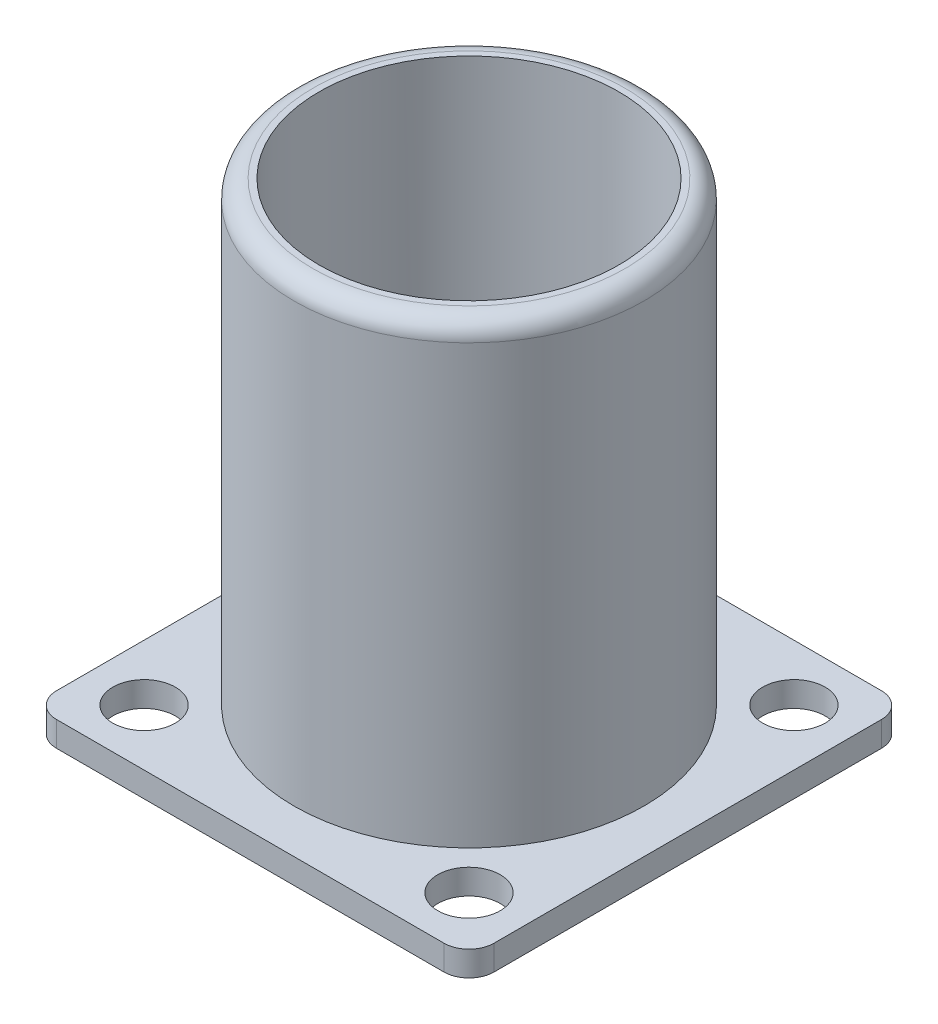
SolidWorks part; units mm, degrees
ref_plane "Plano frontal" through (0, 0, 0) normal (0, 0, 1) x (1, 0, 0)
ref_plane "Plano superior" through (0, 0, 0) normal (0, 1, 0) x (1, 0, 0)
ref_plane "Plano direito" through (0, 0, 0) normal (1, 0, 0) x (0, 0, -1)
sketch "Esboço1" plane through (0, 0, 0) normal (0, 1, 0) x (1, 0, 0)
  line L0 (0, 0) -> (17.5, 0) construction
  line L1 (-17.5, -17.5) -> (17.5, -17.5)
  line L2 (-17.5, -17.5) -> (-17.5, 17.5)
  line L3 (-17.5, 17.5) -> (17.5, 17.5)
  line L4 (17.5, -17.5) -> (17.5, 17.5)
  line L5 (-17.5, -17.5) -> (17.5, 17.5) construction
  line L6 (-17.5, 17.5) -> (17.5, -17.5) construction
  line L7 (-17.5, -13) -> (-13, -13) construction
  line L8 (-17.5, -13) -> (-17.5, -17.5) construction
  line L9 (-17.5, -17.5) -> (-13, -17.5) construction
  line L10 (-13, -13) -> (-13, -17.5) construction
  line L11 (-17.5, -13) -> (-13, -17.5) construction
  line L12 (-17.5, -17.5) -> (-13, -13) construction
  line L13 (0, 0) -> (0, -17.5) construction
  line L14 (0, 0) -> (0, 17.5) construction
  line L15 (-0.75, -11.9765) -> (-0.75, 12)
  line L16 (-12, -12) -> (-10.7087, -12) construction
  line L17 (-12, -12) -> (-12, 12) construction
  line L18 (-12, 12) -> (-0.75, 12) construction
  line L19 (12, -12) -> (12, 12) construction
  line L20 (-12, -12) -> (12, 12) construction
  line L21 (-12, 12) -> (12, -12) construction
  line L22 (0.75, -11.9765) -> (0.75, 12)
  line L23 (0.75, 0) -> (0.75, 17.5) construction
  line L24 (-0.75, 0) -> (-0.75, 17.5) construction
  line L25 (0.75, 12) -> (0.75, 17.5) construction
  line L26 (-0.75, 12) -> (-0.75, 17.5) construction
  line L27 (0.75, -11.9765) -> (0.75, 12)
  line L28 (2.25, -11.9765) -> (2.25, 12)
  line L29 (2.25, -11.9765) -> (2.25, 12)
  line L30 (3.75, -11.9765) -> (3.75, 12)
  line L31 (3.75, -11.9765) -> (3.75, 12)
  line L32 (5.25, -11.9765) -> (5.25, 12)
  line L33 (5.25, -11.9765) -> (5.25, 12)
  line L34 (6.75, -11.9765) -> (6.75, 12)
  line L35 (6.75, -11.9765) -> (6.75, 12)
  line L36 (8.25, -11.9765) -> (8.25, 12)
  line L37 (8.25, -11.9765) -> (8.25, 12)
  line L38 (9.75, -11.9765) -> (9.75, 12)
  line L39 (9.75, -11.9765) -> (9.75, 12)
  line L40 (11.25, -11.9765) -> (11.25, 12)
  line L41 (0, -11.9765) -> (0.75, -11.9765) construction
  line L42 (0, 12) -> (0.75, 12) construction
  line L43 (0.75, 12) -> (12, 12) construction
  line L44 (-0.75, 12) -> (0, 12) construction
  line L45 (-10.7087, -12) -> (0, -12) construction
  line L46 (0, -12) -> (12, -12) construction
  line L47 (-0.75, -11.9765) -> (0, -11.9765) construction
  line L48 (-11.25, -11.9765) -> (-11.25, 12)
  line L49 (-9.75, -11.9765) -> (-9.75, 12)
  line L50 (-8.25, -11.9765) -> (-8.25, 12)
  line L51 (-6.75, -11.9765) -> (-6.75, 12)
  line L52 (-5.25, -11.9765) -> (-5.25, 12)
  line L53 (-3.75, -11.9765) -> (-3.75, 12)
  line L54 (-2.25, -11.9765) -> (-2.25, 12)
  circle A0 centre (-13, -13) radius 2.5
  circle A1 centre (13, -13) radius 2.5
  circle A2 centre (13, 13) radius 2.5
  circle A3 centre (-13, 13) radius 2.5
  arc A4 (-0.75, 11.9765) -> (-2.25, 11.7872) centre (0, 0) ccw
  arc A5 (0.75, 11.9765) -> (0, 12) centre (0, 0) ccw construction
  arc A6 (0, 12) -> (-0.75, 11.9765) centre (0, 0) ccw construction
  arc A7 (-0.75, -11.9765) -> (0, -12) centre (0, 0) ccw construction
  arc A8 (0, -12) -> (2.25, -11.7872) centre (0, 0) ccw
  arc A9 (2.25, -11.7872) -> (3.75, -11.399) centre (0, 0) ccw construction
  arc A10 (3.75, -11.399) -> (5.25, -10.7906) centre (0, 0) ccw
  arc A11 (3.75, 11.399) -> (2.25, 11.7872) centre (0, 0) ccw construction
  arc A12 (2.25, 11.7872) -> (0.75, 11.9765) centre (0, 0) ccw
  arc A13 (6.75, 9.9216) -> (5.25, 10.7906) centre (0, 0) ccw construction
  arc A14 (5.25, 10.7906) -> (3.75, 11.399) centre (0, 0) ccw
  arc A15 (5.25, -10.7906) -> (6.75, -9.9216) centre (0, 0) ccw construction
  arc A16 (6.75, -9.9216) -> (8.4853, -8.4853) centre (0, 0) ccw
  arc A17 (9.75, 6.9955) -> (8.4853, 8.4853) centre (0, 0) ccw construction
  arc A18 (8.4853, 8.4853) -> (6.75, 9.9216) centre (0, 0) ccw
  arc A19 (8.4853, -8.4853) -> (9.75, -6.9955) centre (0, 0) ccw construction
  arc A20 (9.75, -6.9955) -> (11.25, -4.1758) centre (0, 0) ccw
  arc A21 (12, 0) -> (11.25, 4.1758) centre (0, 0) ccw construction
  arc A22 (11.25, 4.1758) -> (9.75, 6.9955) centre (0, 0) ccw
  arc A23 (11.25, -4.1758) -> (12, 0) centre (0, 0) ccw construction
  arc A24 (-2.25, 11.7872) -> (-3.75, 11.399) centre (0, 0) ccw construction
  arc A25 (-3.75, 11.399) -> (-5.25, 10.7906) centre (0, 0) ccw
  arc A26 (-3.75, -11.399) -> (-2.25, -11.7872) centre (0, 0) ccw construction
  arc A27 (-2.25, -11.7872) -> (-0.75, -11.9765) centre (0, 0) ccw
  arc A28 (-6.75, -9.9216) -> (-5.25, -10.7906) centre (0, 0) ccw construction
  arc A29 (-5.25, -10.7906) -> (-3.75, -11.399) centre (0, 0) ccw
  arc A30 (-5.25, 10.7906) -> (-6.75, 9.9216) centre (0, 0) ccw construction
  arc A31 (-6.75, 9.9216) -> (-8.4853, 8.4853) centre (0, 0) ccw
  arc A32 (-8.4853, 8.4853) -> (-9.75, 6.9955) centre (0, 0) ccw construction
  arc A33 (-9.75, 6.9955) -> (-11.25, 4.1758) centre (0, 0) ccw
  arc A34 (-9.75, -6.9955) -> (-8.4853, -8.4853) centre (0, 0) ccw construction
  arc A35 (-8.4853, -8.4853) -> (-6.75, -9.9216) centre (0, 0) ccw
  arc A36 (-12, 0) -> (-11.25, -4.1758) centre (0, 0) ccw construction
  arc A37 (-11.25, -4.1758) -> (-9.75, -6.9955) centre (0, 0) ccw
  arc A38 (-11.25, 4.1758) -> (-12, 0) centre (0, 0) ccw construction
  point P0 (0, 0)
  point P6 (-15.25, -15.25)
  dimension "D3" = 5
  dimension "D4" = 24
  dimension "D1" = 35
  dimension "D2" = 4.5
  dimension "D8" = 1.5
  dimension "D5" = 0.75
  dimension "D6" = 0.75
  dimension "D7" = 8
extrude "Ressalto-extrusão1" add sketch "Esboço1" along normal blind 2 contours L1 L4 L3 L2 A22 A2 L40 A1 A20 L39 A18 L37 A16 L35 A14 L33 A10 L31 A12 region at (0, 0, 0)
ref_plane "Plano1" through (0, 2, 0) normal (0, 1, 0) x (1, 0, 0)
fillet "Filete2" radius 2 4 edges at (-17.5, 1, 17.5) (17.5, 1, 17.5) (17.5, 1, -17.5) (-17.5, 1, -17.5)
sketch "Esboço3" plane through (0, 2, 0) normal (0, 1, 0) x (1, 0, 0)
  circle A0 centre (0, 0) radius 12
  arc A1 (-0.75, 11.9765) -> (-2.25, 11.7872) centre (0, 0) ccw construction
  circle A2 centre (0, 0) radius 14
  dimension "D1" = 2
extrude "Ressalto-extrusão3" add sketch "Esboço3" along normal blind 36.5
fillet "Filete3" radius 1.5 1 edges at (0, 38.5, 14)
equation "\"D6@Esboço1\"=\"D5@Esboço1\""
